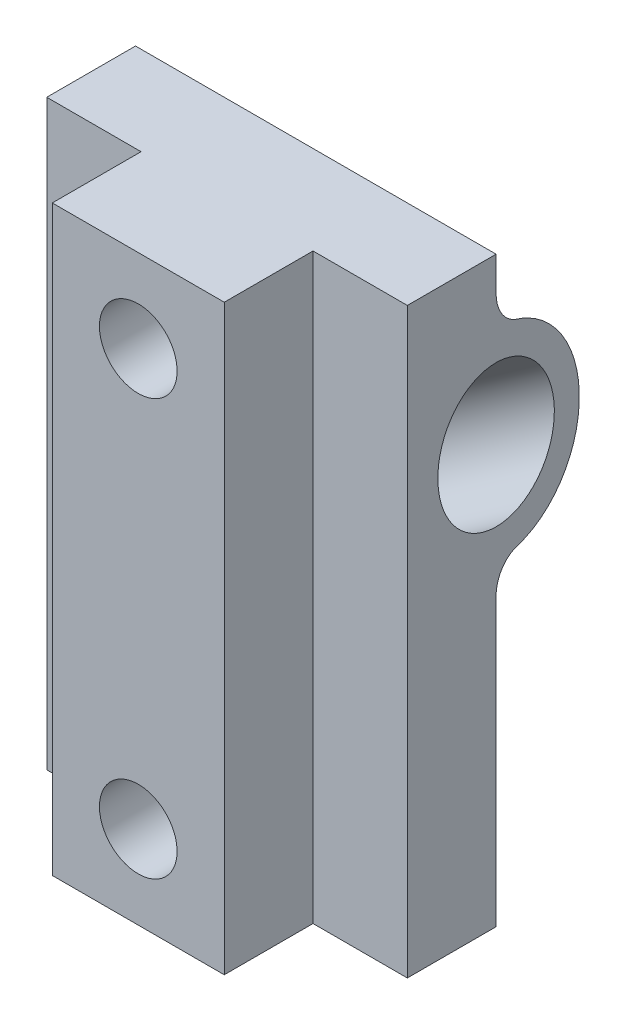
SolidWorks part; units mm, degrees
ref_plane "Front Plane" through (0, 0, 0) normal (0, 0, 1) x (1, 0, 0)
ref_plane "Top Plane" through (0, 0, 0) normal (0, 1, 0) x (1, 0, 0)
ref_plane "Right Plane" through (0, 0, 0) normal (1, 0, 0) x (0, 0, -1)
sketch "Sketch1" plane through (0, 0, 0) normal (0, 1, 0) x (1, 0, 0)
  line L1 (-32.5, 8) -> (32.5, 8)
  line L2 (-32.5, 8) -> (-32.5, -8)
  line L3 (-32.5, -8) -> (32.5, -8)
  line L4 (32.5, 8) -> (32.5, -8)
  line L5 (-32.5, 8) -> (32.5, -8) construction
  line L6 (-32.5, -8) -> (32.5, 8) construction
  line L7 (-15.5, 8) -> (15.5, 8)
  line L8 (-15.5, 8) -> (-15.5, -24)
  line L9 (-15.5, -24) -> (15.5, -24)
  line L10 (15.5, 8) -> (15.5, -24)
  line L11 (-15.5, 8) -> (15.5, -24) construction
  line L12 (-15.5, -24) -> (15.5, 8) construction
  point P0 (0, 0)
  point P6 (0, -8)
  point P11 (0, 0)
  point P12 (0, 0)
  point P13 (0, 0)
  dimension "D1" = 31
  dimension "D2" = 65
  dimension "D3" = 16
  dimension "D4" = 32
extrude "Boss-Extrude1" add sketch "Sketch1" along normal blind 105 contours L8 L1 L2 L3 | L10 L1 L8 L3 | L1 L10 L3 L4 | L9 L10 L7 L8 region at (-24, 0, 0) region at (0, 0, 0) region at (24, 0, 0)
sketch "Sketch2" plane through (0, 0, -8) normal (0, 0, -1) x (-1, 0, 0)
  line L0 (0, 0) -> (0, 105) construction
  line L1 (32.5, 0) -> (-32.5, 0) construction
  line L2 (32.5, 105) -> (-32.5, 105) construction
  line L3 (0, 52.5) -> (-18.6301, 52.5) construction
  circle A0 centre (0, 90) radius 7
  circle A1 centre (0, 15) radius 7
  dimension "D1" = 14
  dimension "D2" = 75
extrude "Cut-Extrude1" cut sketch "Sketch2" against normal blind 105
ref_plane "Plane1" through (27.526, 19.2739, 0) normal (-0.8192, -0.5736, 0) x (0, 0, 1)
sketch "Sketch9" plane through (0, 0, -8) normal (0, 0, -1) x (-1, 0, 0)
  line L0 (0, 105) -> (0, 0) construction
  line L1 (32.5, 105) -> (-32.5, 105) construction
  line L2 (0, 0) -> (0, 52.5) construction
  line L3 (0, 52.5) -> (32.5, 29.7433) construction
  line L4 (32.5, 105) -> (32.5, 0) construction
  line L5 (32.5, 29.7433) -> (0, 52.5) construction
  line L6 (0, 52.5) -> (9.3665, 65.8768) construction
  dimension "D1" = 35
sketch "Sketch8" plane through (27.526, 19.2739, 0) normal (-0.8192, -0.5736, 0) x (0, 0, 1)
  line L0 (-8, 104.6522) -> (-8, 18.6412) construction
  line L1 (-8, 86.011) -> (-8, 0) construction
  circle A0 centre (-8, 43.0055) radius 10.5
  circle A1 centre (-8, 43.0055) radius 15
  point P5 (-8, 43.0055)
  dimension "D1" = 21
  dimension "D2" = 30
extrude "Boss-Extrude2" add sketch "Sketch8" along normal up to surface and the other way up to surface up to face at (-32.5, 52.5, 0) other way up to face at (32.5, 52.5, 0)
extrude "Cut-Extrude2" cut sketch "Sketch8<2>" against normal through all both and the other way through all contours A0 region at (2.8591, 54.502, -8)
sketch "Sketch8<2>" plane through (27.526, 19.2739, 0) normal (-0.8192, -0.5736, 0) x (0, 0, 1) same geometry as "Sketch8"
fillet "Fillet2" radius 5 2 edges at (0, 70.8116, -8) (0, 34.1884, -8)
